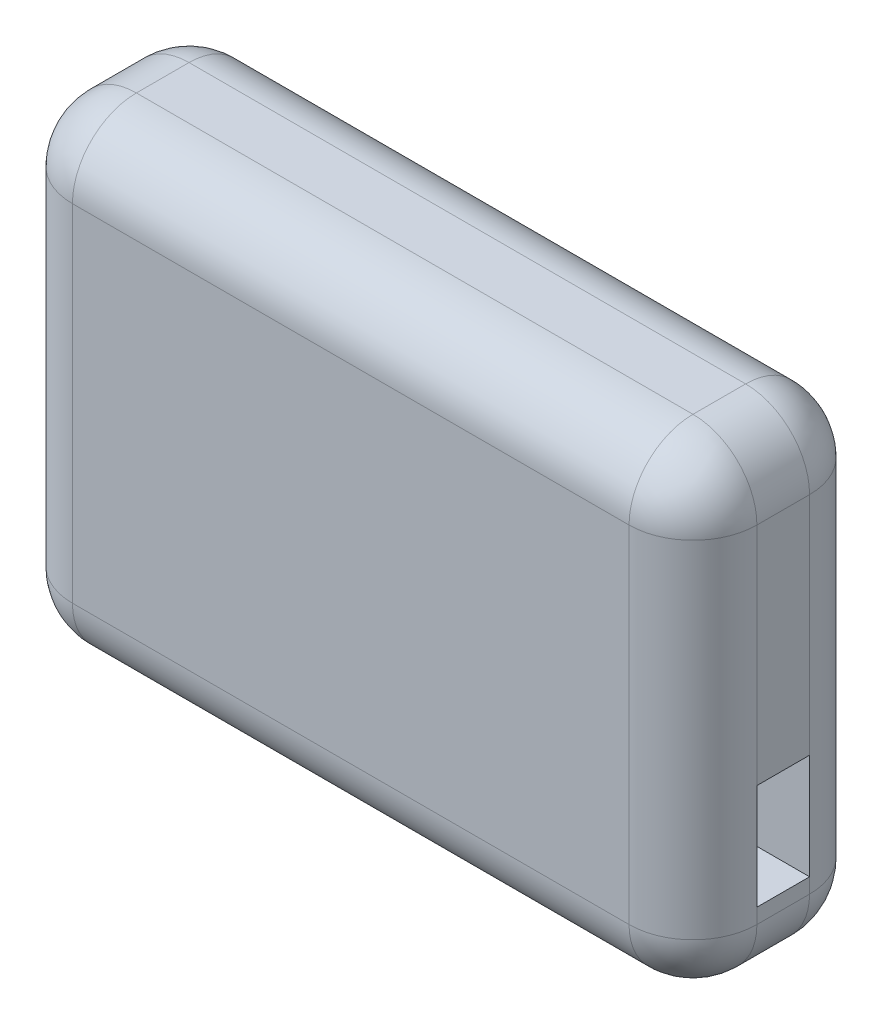
SolidWorks part; units mm, degrees
ref_plane "Front Plane" through (0, 0, 0) normal (0, 0, 1) x (1, 0, 0)
ref_plane "Top Plane" through (0, 0, 0) normal (0, 1, 0) x (1, 0, 0)
ref_plane "Right Plane" through (0, 0, 0) normal (1, 0, 0) x (0, 0, -1)
sketch "Sketch1" plane through (0, 0, 0) normal (0, 0, 1) x (1, 0, 0)
  line L1 (-45.5, -31.5) -> (45.5, -31.5)
  line L2 (-45.5, -31.5) -> (-45.5, 31.5)
  line L3 (-45.5, 31.5) -> (45.5, 31.5)
  line L4 (45.5, -31.5) -> (45.5, 31.5)
  line L5 (-45.5, -31.5) -> (45.5, 31.5) construction
  line L6 (-45.5, 31.5) -> (45.5, -31.5) construction
  point P0 (0, 0)
  dimension "D1" = 91
  dimension "D2" = 63
extrude "Boss-Extrude1" add sketch "Sketch1" along normal blind 12 and the other way blind 12
fillet "Fillet1" radius 8.5 8 edges at (0, 31.5, -12) (-45.5, 0, -12) (0, -31.5, -12) (45.5, 0, -12) (0, -31.5, 12) (-45.5, 0, 12) (0, 31.5, 12) (45.5, 0, 12)
fillet "Fillet2" radius 8.5 12 edges at (43.0104, -29.0104, -9.5104) (43.0104, -29.0104, 9.5104) (-43.0104, -29.0104, -9.5104) (-43.0104, -29.0104, 9.5104) (43.0104, 29.0104, -9.5104) (43.0104, 29.0104, 9.5104) (-43.0104, 29.0104, -9.5104) (-43.0104, 29.0104, 9.5104) (45.5, -31.5, 0) (-45.5, -31.5, 0) (45.5, 31.5, 0) (-45.5, 31.5, 0)
sketch "Sketch2" plane through (45.5, 0, 0) normal (1, 0, 0) x (0, 0, -1)
  line L5 (-3.5, 23) -> (-3.5, -23) construction
  line L6 (-3.5, -7) -> (3.5, -7)
  line L8 (-3.5, -7) -> (-3.5, -21)
  line L9 (-3.5, -21) -> (3.5, -21)
  line L10 (3.5, -7) -> (3.5, -21)
  line L11 (3.5, -23) -> (3.5, 23) construction
  line L12 (-3.5, -23) -> (3.5, -23) construction
  dimension "D1" = 14
  dimension "D2" = 2
extrude "Cut-Extrude1" cut sketch "Sketch2" against normal blind 12
